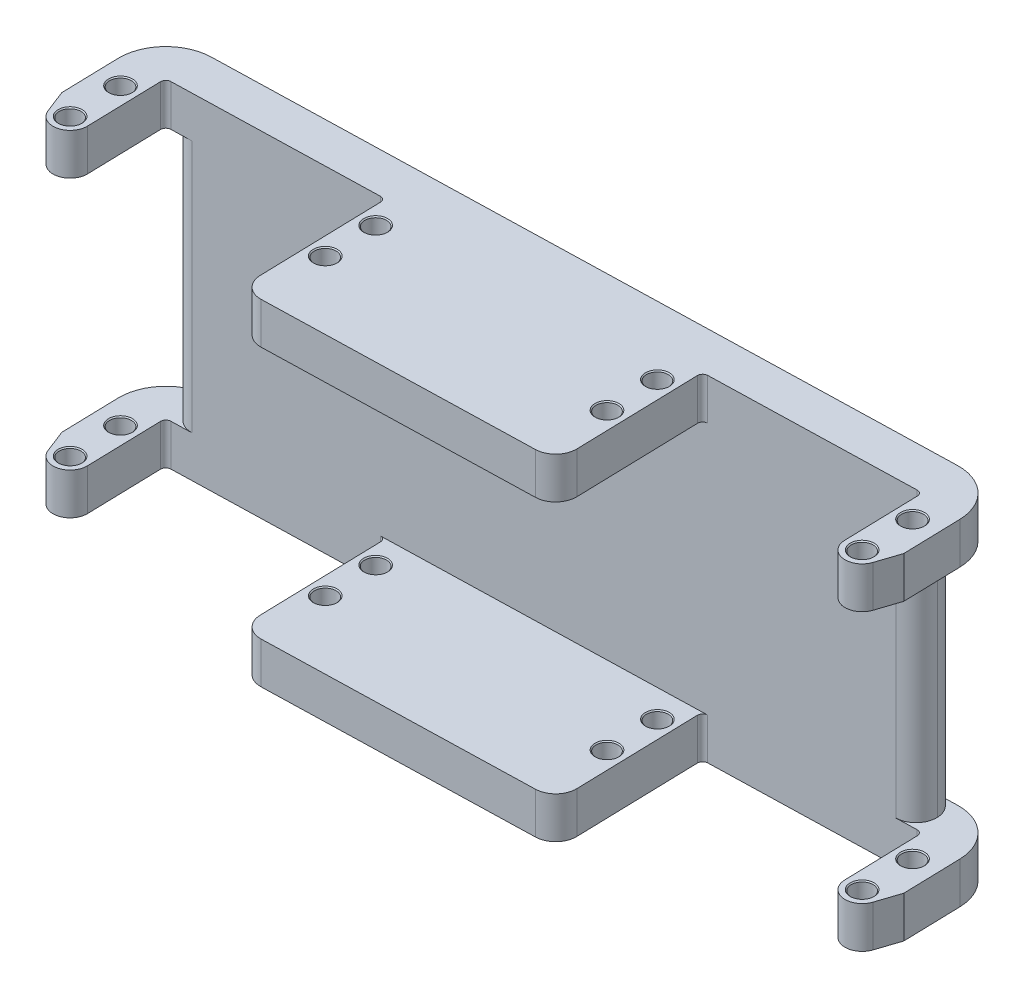
SolidWorks part; units mm, degrees
ref_plane "Front Plane" through (0, 0, 0) normal (0, 0, 1) x (1, 0, 0)
ref_plane "Top Plane" through (0, 0, 0) normal (0, 1, 0) x (1, 0, 0)
ref_plane "Right Plane" through (0, 0, 0) normal (1, 0, 0) x (0, 0, -1)
sketch "Sketch1" plane through (0, 0, 0) normal (0, 1, 0) x (1, 0, 0)
  line L0 (22.9808, 0.3288) -> (29.7784, 0.5103) construction
  line L1 (29.7784, 0.5103) -> (29.545, 9.2572) construction
  line L2 (29.545, 9.2572) -> (23.747, 9.1024) construction
  line L3 (22.7741, 8.0761) -> (22.8274, 6.0768) construction
  line L4 (22.8274, 6.0768) -> (24.4394, 6.1198) construction
  line L5 (24.5061, 3.6207) -> (22.8941, 3.5777) construction
  line L6 (22.8941, 3.5777) -> (22.9808, 0.3288) construction
  line L7 (29.8051, -0.4894) -> (23.0075, -0.6708) construction
  line L8 (23.0075, -0.6708) -> (23.0942, -3.9196) construction
  line L9 (23.0942, -3.9196) -> (24.7062, -3.8766) construction
  line L10 (24.7729, -6.3757) -> (23.1609, -6.4188) construction
  line L11 (23.1609, -6.4188) -> (23.2143, -8.418) construction
  line L12 (24.2406, -9.391) -> (30.0386, -9.2362) construction
  line L13 (30.0386, -9.2362) -> (29.8051, -0.4894) construction
  line L14 (77.5881, 0.786) -> (70.7905, 0.6046) construction
  line L15 (70.7905, 0.6046) -> (71.024, -8.1423) construction
  line L16 (71.024, -8.1423) -> (76.8219, -7.9875) construction
  line L17 (77.7949, -6.9612) -> (77.7415, -4.9619) construction
  line L18 (77.7415, -4.9619) -> (76.1295, -5.005) construction
  line L19 (76.0628, -2.5058) -> (77.6748, -2.4628) construction
  line L20 (77.6748, -2.4628) -> (77.5881, 0.786) construction
  line L21 (70.7638, 1.6042) -> (77.5614, 1.7857) construction
  line L22 (77.5614, 1.7857) -> (77.4747, 5.0345) construction
  line L23 (77.4747, 5.0345) -> (75.8627, 4.9915) construction
  line L24 (75.796, 7.4906) -> (77.408, 7.5336) construction
  line L25 (77.408, 7.5336) -> (77.3546, 9.5329) construction
  line L26 (76.3283, 10.5059) -> (70.5304, 10.3511) construction
  line L27 (70.5304, 10.3511) -> (70.7638, 1.6042) construction
  line L28 (-23.376, -1.9088) -> (-30.1735, -2.0903) construction
  line L29 (-30.1735, -2.0903) -> (-29.9401, -10.8372) construction
  line L30 (-29.9401, -10.8372) -> (-24.1421, -10.6824) construction
  line L31 (-23.1692, -9.6561) -> (-23.2225, -7.6568) construction
  line L32 (-23.2225, -7.6568) -> (-24.8345, -7.6998) construction
  line L33 (-24.9012, -5.2007) -> (-23.2892, -5.1577) construction
  line L34 (-23.2892, -5.1577) -> (-23.376, -1.9088) construction
  line L35 (-30.2002, -1.0906) -> (-23.4026, -0.9092) construction
  line L36 (-23.4026, -0.9092) -> (-23.4894, 2.3397) construction
  line L37 (-23.4894, 2.3397) -> (-25.1013, 2.2966) construction
  line L38 (-25.168, 4.7957) -> (-23.5561, 4.8388) construction
  line L39 (-23.5561, 4.8388) -> (-23.6094, 6.8381) construction
  line L40 (-24.6358, 7.811) -> (-30.4337, 7.6563) construction
  line L41 (-30.4337, 7.6563) -> (-30.2002, -1.0906) construction
  line L42 (-77.9832, -2.366) -> (-71.1856, -2.1846) construction
  line L43 (-71.1856, -2.1846) -> (-71.4191, 6.5623) construction
  line L44 (-71.4191, 6.5623) -> (-77.217, 6.4076) construction
  line L45 (-78.19, 5.3812) -> (-78.1366, 3.3819) construction
  line L46 (-78.1366, 3.3819) -> (-76.5247, 3.425) construction
  line L47 (-76.4579, 0.9259) -> (-78.0699, 0.8828) construction
  line L48 (-78.0699, 0.8828) -> (-77.9832, -2.366) construction
  line L49 (-71.1589, -3.1842) -> (-77.9565, -3.3657) construction
  line L50 (-77.9565, -3.3657) -> (-77.8698, -6.6145) construction
  line L51 (-77.8698, -6.6145) -> (-76.2578, -6.5715) construction
  line L52 (-76.1911, -9.0706) -> (-77.8031, -9.1136) construction
  line L53 (-77.8031, -9.1136) -> (-77.7497, -11.1129) construction
  line L54 (-76.7234, -12.0859) -> (-70.9255, -11.9311) construction
  line L55 (-70.9255, -11.9311) -> (-71.1589, -3.1842) construction
  line L56 (70.2509, -9.1633) -> (30.865, -10.2145) construction
  line L57 (30.318, 10.2782) -> (69.704, 11.3294) construction
  line L58 (-70.6461, 7.5833) -> (-31.2601, 8.6346) construction
  line L59 (-30.7131, -11.8581) -> (-70.1179, -12.9099) construction
  line L60 (-71.4244, 6.7622) -> (-71.4191, 6.5623) construction
  line L61 (-70.9255, -11.9311) -> (-70.9255, -12.1235) construction
  line L62 (70.525, 10.551) -> (70.5304, 10.3511) construction
  line L63 (71.024, -8.1423) -> (71.0293, -8.3422) construction
  line L64 (-70.6514, 7.7832) -> (-31.2654, 8.8345)
  line L65 (-30.7078, -12.0581) -> (-70.1125, -13.1098)
  line L66 (70.2563, -9.3632) -> (30.8703, -10.4145)
  line L67 (-71.6244, 6.7569) -> (-71.1255, -12.1235)
  line L68 (-30.439, 7.8562) -> (-30.4337, 7.6563) construction
  line L69 (-29.9401, -10.8372) -> (-29.9347, -11.0371) construction
  line L70 (30.3126, 10.4781) -> (69.6986, 11.5293)
  line L71 (70.7249, 10.5564) -> (71.2292, -8.3369)
  line L72 (-23.4026, -0.9092) -> (23.0075, -0.6708) construction
  line L73 (22.9808, 0.3288) -> (-23.376, -1.9088) construction
  line L74 (78.7221, 10.7698) -> (79.2264, -8.1234)
  line L75 (70.4697, -17.3604) -> (31.0838, -18.4116)
  line L76 (-30.4943, -20.0552) -> (31.0838, -18.4116)
  line L77 (-30.4943, -20.0552) -> (-69.8991, -21.107)
  line L78 (-79.6215, 6.5445) -> (-79.1241, -12.2823)
  line L79 (-70.8648, 15.7804) -> (-35.4663, 16.7252)
  line L80 (-35.4663, 16.7252) -> (69.4852, 19.5265)
  line L81 (-29.7348, -11.0317) -> (-30.2391, 7.8615)
  line L82 (29.5396, 9.4571) -> (29.545, 9.2572) construction
  line L83 (30.0386, -9.2362) -> (30.0439, -9.4362) construction
  line L84 (29.844, -9.4415) -> (29.3397, 9.4518)
  arc A0 (23.747, 9.1024) -> (22.7741, 8.0761) centre (23.7737, 8.1028) ccw construction
  arc A1 (24.5061, 3.6207) -> (24.4394, 6.1198) centre (26.1596, 4.9153) ccw construction
  arc A2 (24.7729, -6.3757) -> (24.7062, -3.8766) centre (26.4264, -5.0811) ccw construction
  arc A3 (23.2143, -8.418) -> (24.2406, -9.391) centre (24.2139, -8.3914) ccw construction
  arc A4 (76.8219, -7.9875) -> (77.7949, -6.9612) centre (76.7952, -6.9879) ccw construction
  arc A5 (76.0628, -2.5058) -> (76.1295, -5.005) centre (74.4093, -3.8004) ccw construction
  arc A6 (75.796, 7.4906) -> (75.8627, 4.9915) centre (74.1425, 6.196) ccw construction
  arc A7 (77.3546, 9.5329) -> (76.3283, 10.5059) centre (76.355, 9.5062) ccw construction
  arc A8 (-24.1421, -10.6824) -> (-23.1692, -9.6561) centre (-24.1688, -9.6828) ccw construction
  arc A9 (-24.9012, -5.2007) -> (-24.8345, -7.6998) centre (-26.5547, -6.4953) ccw construction
  arc A10 (-25.168, 4.7957) -> (-25.1013, 2.2966) centre (-26.8215, 3.5012) ccw construction
  arc A11 (-23.6094, 6.8381) -> (-24.6358, 7.811) centre (-24.6091, 6.8114) ccw construction
  arc A12 (-77.217, 6.4076) -> (-78.19, 5.3812) centre (-77.1903, 5.4079) ccw construction
  arc A13 (-76.4579, 0.9259) -> (-76.5247, 3.425) centre (-74.8044, 2.2204) ccw construction
  arc A14 (-76.1911, -9.0706) -> (-76.2578, -6.5715) centre (-74.5376, -7.776) ccw construction
  arc A15 (-77.7497, -11.1129) -> (-76.7234, -12.0859) centre (-76.7501, -11.0862) ccw construction
  arc A16 (-30.7131, -11.8581) -> (-29.9347, -11.0371) centre (-30.7345, -11.0584) ccw construction
  arc A17 (-30.439, 7.8562) -> (-31.2601, 8.6346) centre (-31.2387, 7.8348) ccw construction
  arc A18 (-70.6461, 7.5833) -> (-71.4244, 6.7622) centre (-70.6247, 6.7836) ccw construction
  arc A19 (70.2509, -9.1633) -> (71.0293, -8.3422) centre (70.2296, -8.3636) ccw construction
  arc A20 (70.525, 10.551) -> (69.704, 11.3294) centre (69.7253, 10.5297) ccw construction
  arc A21 (30.318, 10.2782) -> (29.5396, 9.4571) centre (30.3393, 9.4784) ccw construction
  arc A22 (30.0439, -9.4362) -> (30.865, -10.2145) centre (30.8436, -9.4148) ccw construction
  arc A23 (-70.9255, -12.1235) -> (-70.1179, -12.9099) centre (-70.1388, -12.1235) ccw construction
  arc A24 (78.7221, 10.7698) -> (69.4852, 19.5265) centre (69.7253, 10.5297) ccw
  arc A25 (-70.6514, 7.7832) -> (-71.6244, 6.7569) centre (-70.6247, 6.7836) ccw
  arc A26 (-71.1255, -12.1235) -> (-70.1125, -13.1098) centre (-70.1388, -12.1235) ccw
  arc A27 (70.4697, -17.3604) -> (79.2264, -8.1234) centre (70.2296, -8.3636) ccw
  arc A28 (-79.1241, -12.2823) -> (-69.8991, -21.107) centre (-70.1388, -12.1235) ccw
  arc A29 (70.2563, -9.3632) -> (71.2292, -8.3369) centre (70.2296, -8.3636) ccw
  arc A30 (70.7249, 10.5564) -> (69.6986, 11.5293) centre (69.7253, 10.5297) ccw
  arc A31 (-70.8648, 15.7804) -> (-79.6215, 6.5445) centre (-70.6247, 6.7836) ccw
  circle A32 centre (-74.8044, 2.2204) radius 2.1
  circle A33 centre (-74.5376, -7.776) radius 2.1
  circle A34 centre (-26.8215, 3.5012) radius 2.1
  circle A35 centre (-26.5547, -6.4953) radius 2.1
  circle A36 centre (26.1596, 4.9153) radius 2.1
  circle A37 centre (26.4264, -5.0811) radius 2.1
  circle A38 centre (74.1425, 6.196) radius 2.1
  circle A39 centre (74.4093, -3.8004) radius 2.1
  arc A40 (-30.2391, 7.8615) -> (-31.2654, 8.8345) centre (-31.2387, 7.8348) ccw
  arc A41 (-30.7078, -12.0581) -> (-29.7348, -11.0317) centre (-30.7345, -11.0584) ccw
  arc A42 (30.3126, 10.4781) -> (29.3397, 9.4518) centre (30.3393, 9.4784) ccw
  arc A43 (29.844, -9.4415) -> (30.8703, -10.4145) centre (30.8436, -9.4148) ccw
  point P129 (-0.1976, -0.79)
extrude "Boss-Extrude1" add sketch "Sketch1" along normal blind 8 contours L79 A31 L78 A28 L77 L76 L75 A27 L74 A24 L80 A43 L84 A42 L70 A30 L71 A29 L66 A41 L65 A26 L67 A25 L64 A40 L81 A39 A38 A37 A36 A35 A34 A33 A32 region at (-0.1994, 0, 0.7904)
sketch "Sketch3" plane through (0, 8, 0) normal (0, 1, 0) x (1, 0, 0)
  line L0 (-29.7348, -11.0317) -> (-30.2391, 7.8615) construction
  line L1 (-29.4947, -20.0285) -> (-30.2391, 7.8615)
  line L2 (-71.6244, 6.7569) -> (-71.1255, -12.1235) construction
  line L3 (-71.6244, 6.7569) -> (-70.8889, -21.0788)
  line L4 (70.4697, -17.3604) -> (-69.8991, -21.107) construction
  line L5 (-29.4947, -20.0285) -> (-69.8991, -21.107)
  line L6 (-71.6244, 6.7569) -> (-30.2391, 7.8615)
  line L7 (29.844, -9.4415) -> (29.3397, 9.4518) construction
  line L8 (30.0841, -18.4383) -> (29.3397, 9.4518)
  line L9 (70.7249, 10.5564) -> (71.2292, -8.3369) construction
  line L10 (70.7249, 10.5564) -> (71.4679, -17.278)
  line L11 (29.3397, 9.4518) -> (70.7249, 10.5564)
  line L12 (30.0841, -18.4383) -> (70.4697, -17.3604)
  arc A0 (-79.1241, -12.2823) -> (-69.8991, -21.107) centre (-70.1388, -12.1235) ccw construction
  arc A1 (-70.8889, -21.0788) -> (-69.8991, -21.107) centre (-70.1388, -12.1235) ccw
  arc A2 (70.4697, -17.3604) -> (79.2264, -8.1234) centre (70.2296, -8.3636) ccw construction
  arc A3 (70.4697, -17.3604) -> (71.4679, -17.278) centre (70.2296, -8.3636) ccw
extrude "Cut-Extrude1" cut sketch "Sketch3" against normal through all both and the other way through all
fillet "Fillet1" radius 4 4 edges at (71.4679, 4, 17.278) (30.0841, 4, 18.4383) (-29.4947, 4, 20.0285)
sketch "Sketch4" plane through (0, 0, 0) normal (0, 1, 0) x (1, 0, 0)
  line L0 (69.4852, 19.5265) -> (69.6986, 11.5293)
  line L1 (-70.8648, 15.7804) -> (-70.6514, 7.7832)
  line L11 (70.7249, 10.5564) -> (71.2292, -8.3369)
  line L12 (79.2264, -8.1234) -> (78.7221, 10.7698)
  line L13 (69.4852, 19.5265) -> (-70.8648, 15.7804)
  line L14 (-79.6216, 6.5459) -> (-79.1241, -12.2823)
  line L15 (-71.1232, -12.2082) -> (-71.1241, -12.1757)
  line L16 (-71.1255, -12.1235) -> (-71.6244, 6.7572)
  line L17 (-70.6514, 7.7832) -> (-31.2654, 8.8345)
  line L18 (-30.2391, 7.8615) -> (-29.6014, -16.03)
  line L19 (-25.4961, -19.9218) -> (26.0855, -18.545)
  line L20 (29.9774, -14.4397) -> (29.3397, 9.4518)
  line L21 (30.3126, 10.4781) -> (69.6986, 11.5293)
  line L24 (69.4852, 19.5265) -> (-70.8648, 15.7804)
  line L28 (-70.6514, 7.7832) -> (69.6986, 11.5293)
  arc A12 (71.2292, -8.3369) -> (79.2264, -8.1234) centre (75.2278, -8.2302) ccw
  arc A13 (78.7221, 10.7698) -> (69.4852, 19.5265) centre (69.7253, 10.5297) ccw
  arc A14 (-70.8648, 15.7804) -> (-79.6216, 6.5459) centre (-70.6247, 6.7836) ccw
  arc A15 (-79.1241, -12.2823) -> (-79.1189, -12.4665) centre (-70.1388, -12.1235) ccw
  arc A16 (-79.1189, -12.4665) -> (-71.1232, -12.2082) centre (-75.1218, -12.3138) ccw
  arc A17 (-71.1255, -12.1235) -> (-71.1241, -12.1757) centre (-70.1388, -12.1235) ccw
  arc A18 (-70.6514, 7.7832) -> (-71.6244, 6.7572) centre (-70.6247, 6.7836) ccw
  arc A19 (-30.2391, 7.8615) -> (-31.2654, 8.8345) centre (-31.2387, 7.8348) ccw
  arc A20 (-29.6014, -16.03) -> (-25.4961, -19.9218) centre (-25.6028, -15.9232) ccw
  arc A21 (26.0855, -18.545) -> (29.9774, -14.4397) centre (25.9788, -14.5465) ccw
  arc A22 (30.3126, 10.4781) -> (29.3397, 9.4518) centre (30.3393, 9.4784) ccw
  arc A23 (70.7249, 10.5564) -> (69.6986, 11.5293) centre (69.7253, 10.5297) ccw
  dimension "D1" = 0
extrude "Boss-Extrude3" add sketch "Sketch4" along normal blind 32.4
fillet "Fillet2" radius 4 4 edges at (-70.6514, 20.2, -7.7832) (-70.8648, 20.2, -15.7804) (69.6986, 20.2, -11.5293) (69.4852, 20.2, -19.5265)
chamfer "Chamfer1" distance 0.2 angle 45 16 edges at (74.4093, 0, 5.9004) (74.4093, 8, 5.9004) (74.1425, 0, -4.096) (74.1425, 8, -4.096) (26.4264, 0, 7.1811) (26.4264, 8, 7.1811) (26.1596, 0, -2.8153) (26.1596, 8, -2.8153) (-26.5547, 0, 8.5953) (-26.5547, 8, 8.5953) (-26.8215, 0, -1.4012) (-26.8215, 8, -1.4012) (-74.5376, 0, 9.876) (-74.5376, 8, 9.876) (-74.8044, 0, -0.1204) (-74.8044, 8, -0.1204)
mirror "Mirror2" about plane through (0, 32.4, 0) normal (0, 1, 0) of bodies 105
sketch "Sketch5" plane through (0, 64.8, 0) normal (0, 1, 0) x (1, 0, 0)
  line L1 (-77.605, -8.9826) -> (-79.3269, -4.6053)
  line L2 (77.5419, -4.8382) -> (79.0196, -0.3774)
  line L3 (-79.3269, -4.6053) -> (-74.6247, -4.481) construction
  line L4 (79.0196, -0.3774) -> (74.4093, -0.5004) construction
  line L5 (-79.6215, 6.5445) -> (-79.1241, -12.2823) construction
  line L12 (-70.6514, 7.7832) -> (-31.2654, 8.8345)
  line L13 (-30.2391, 7.8615) -> (-29.6014, -16.03)
  line L14 (-25.4961, -19.9218) -> (26.0855, -18.545)
  line L15 (29.9774, -14.4397) -> (29.3397, 9.4518)
  line L16 (30.3126, 10.4781) -> (69.6986, 11.5293)
  line L17 (70.7249, 10.5564) -> (71.2292, -8.3369)
  line L18 (79.2264, -8.1234) -> (78.7221, 10.7698)
  line L19 (69.4852, 19.5265) -> (-70.8648, 15.7804)
  line L20 (-79.6215, 6.5445) -> (-79.1241, -12.2823)
  line L21 (-71.1232, -12.2082) -> (-71.1241, -12.1757)
  line L22 (-71.1255, -12.1235) -> (-71.6244, 6.7569)
  line L28 (71.1105, -3.8885) -> (71.2292, -8.3369)
  line L29 (79.2264, -8.1234) -> (79.0196, -0.3774)
  line L31 (-79.3269, -4.6053) -> (-79.1241, -12.2823)
  line L32 (-71.1232, -12.2082) -> (-71.1241, -12.1757)
  line L33 (-71.1255, -12.1235) -> (-71.2427, -7.6889)
  arc A0 (-77.605, -8.9826) -> (-71.2427, -7.6889) centre (-74.5376, -7.776) ccw
  circle A2 centre (74.4093, -3.8004) radius 3.3 construction
  arc A4 (74.4093, -0.5004) -> (71.1105, -3.8885) centre (74.4093, -3.8004) ccw construction
  circle A5 centre (-74.5376, -7.776) radius 2.1 construction
  circle A6 centre (-74.5376, -7.776) radius 2.1 construction
  circle A8 centre (74.4093, -3.8004) radius 2.3 construction
  circle A9 centre (74.4093, -3.8004) radius 2.3 construction
  arc A10 (71.1105, -3.8885) -> (77.5419, -4.8382) centre (74.4093, -3.8004) ccw
  arc A11 (-74.6247, -4.481) -> (-71.2427, -7.6889) centre (-74.5376, -7.776) cw
  arc A20 (-30.2391, 7.8615) -> (-31.2654, 8.8345) centre (-31.2387, 7.8348) ccw
  arc A21 (-29.6014, -16.03) -> (-25.4961, -19.9218) centre (-25.6028, -15.9232) ccw
  arc A22 (26.0855, -18.545) -> (29.9774, -14.4397) centre (25.9788, -14.5465) ccw
  arc A23 (30.3126, 10.4781) -> (29.3397, 9.4518) centre (30.3393, 9.4784) ccw
  arc A24 (70.7249, 10.5564) -> (69.6986, 11.5293) centre (69.7253, 10.5297) ccw
  arc A25 (71.2292, -8.3369) -> (79.2264, -8.1234) centre (75.2278, -8.2302) ccw
  arc A26 (78.7221, 10.7698) -> (69.4852, 19.5265) centre (69.7253, 10.5297) ccw
  arc A27 (-70.8648, 15.7804) -> (-79.6215, 6.5445) centre (-70.6247, 6.7836) ccw
  arc A28 (-79.1241, -12.2823) -> (-79.1189, -12.4665) centre (-70.1388, -12.1235) ccw
  arc A29 (-79.1189, -12.4665) -> (-71.1232, -12.2082) centre (-75.1218, -12.3138) ccw
  arc A30 (-71.1255, -12.1235) -> (-71.1241, -12.1757) centre (-70.1388, -12.1235) ccw
  arc A31 (-70.6514, 7.7832) -> (-71.6244, 6.7569) centre (-70.6247, 6.7836) ccw
  arc A37 (71.2292, -8.3369) -> (79.2264, -8.1234) centre (75.2278, -8.2302) ccw
  arc A40 (-79.1241, -12.2823) -> (-79.1189, -12.4665) centre (-70.1388, -12.1235) ccw
  arc A41 (-79.1189, -12.4665) -> (-71.1232, -12.2082) centre (-75.1218, -12.3138) ccw
  arc A42 (-71.1255, -12.1235) -> (-71.1241, -12.1757) centre (-70.1388, -12.1235) ccw
  line M51 (70.7249, 10.5564) -> (71.2292, -8.3369)
  arc M52 (71.2292, -8.3369) -> (79.2264, -8.1234) centre (75.2278, -8.2302) ccw
  line M53 (79.2264, -8.1234) -> (78.7221, 10.7698)
  line M57 (-79.6215, 6.5445) -> (-79.1241, -12.2823)
  arc M58 (-79.1241, -12.2823) -> (-79.1189, -12.4665) centre (-70.1388, -12.1235) ccw
  arc M59 (-79.1189, -12.4665) -> (-71.1232, -12.2082) centre (-75.1218, -12.3138) ccw
  line M60 (-71.1232, -12.2082) -> (-71.1241, -12.1757)
  arc M61 (-71.1241, -12.1757) -> (-71.1255, -12.1235) centre (-70.1388, -12.1235) cw
  line M62 (-71.1255, -12.1235) -> (-71.6244, 6.7569)
  dimension "D1" = 0
extrude "Cut-Extrude2" cut sketch "Sketch5" against normal through all both and the other way through all contours A0 L1 M57 M58 M59 M60 M61 M62 | A10 L2 M51 M52 M53 region at (-75.5296, 64.8, 12.3994) region at (75.6447, 64.8, 8.3299) body kept at (-70.7581, 8, -11.7819)
ref_plane "MidPlane" through (0, 32.4, 0) normal (0, 1, 0) x (1, 0, 0)
